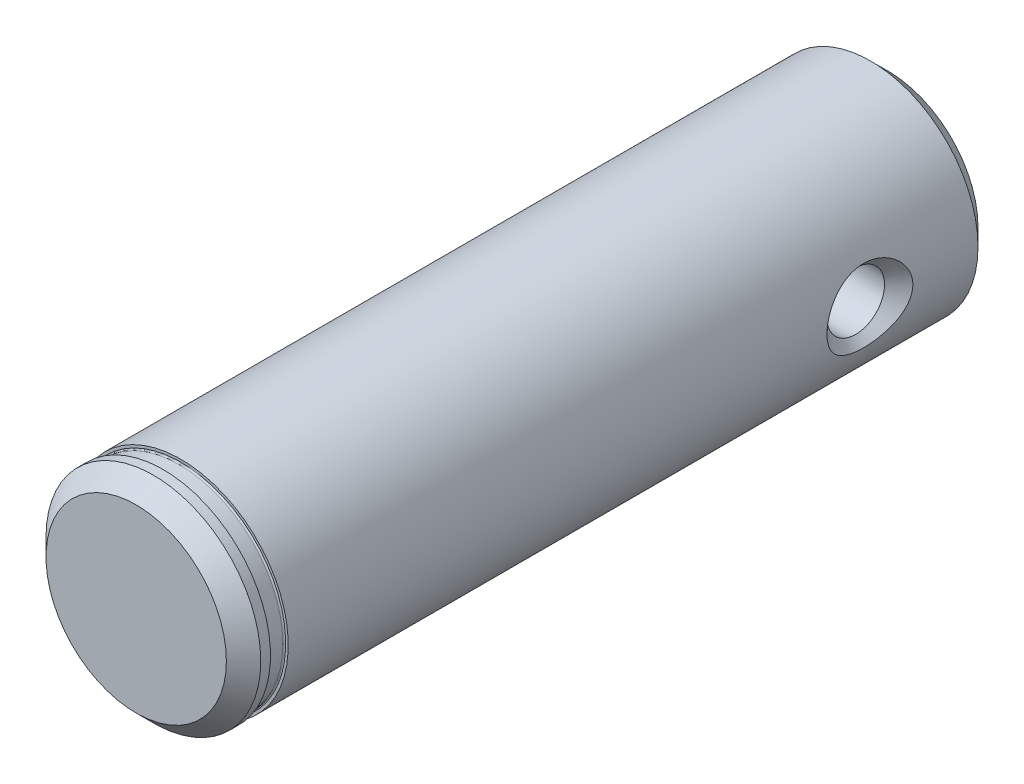
SolidWorks part; units mm, degrees
note: '?' marks a value the reader was unsure of.
ref_plane "Front Plane" through (0, 0, 0) normal (0, 0, 1) x (1, 0, 0)
ref_plane "Top Plane" through (0, 0, 0) normal (0, 1, 0) x (1, 0, 0)
ref_plane "Right Plane" through (0, 0, 0) normal (1, 0, 0) x (0, 0, -1)
sketch "Sketch1" plane through (0, 0, 0) normal (0, 0, 1) x (1, 0, 0)
  circle A0 centre (0, 0) radius 9.525
  dimension "D1" = 19.05
extrude "Boss-Extrude1" add sketch "Sketch1" along normal mid plane 66.675
ref_plane "Plane1" through (-9.525, 0, 0) normal (-1, 0, 0) x (0, 0, 1)
chamfer "Chamfer1" distance 1.524 angle 45 2 edges at (9.525, 0, -33.3375) (9.525, 0, 33.3375)
hole_wizard "1/4-20 Tapped Hole1" positions "Sketch4" profile "Sketch3" tap size "1/4-20" standard "ANSI Inch" end condition through all
sketch "Sketch4" plane through (-9.525, 0, 0) normal (-1, 0, 0) x (0, 0, 1)
  line L0 (-33.3375, 8.001) -> (-33.3375, -8.001) construction
  point P0 (-22.225, 0)
  dimension "D1" = 11.1125
sketch "Sketch3" plane through (-9.525, 0, -22.225) normal (0, 1, 0) x (0, 0, 1)
  line L0 (0, 0) -> (0, 19.05)
  line L1 (0, 19.05) -> (3.81, 19.05)
  line L2 (2.5527, 17.7927) -> (2.5527, 1.2573)
  line L3 (2.5527, 1.2573) -> (3.81, 0)
  line L5 (3.81, 0) -> (0, 0)
  line L6 (-2.5527, 1.2573) -> (-3.81, 0) construction
  line L7 (3.81, 19.05) -> (2.5527, 17.7927)
  line L8 (-3.81, 19.05) -> (-2.5527, 17.7927) construction
  line L11 (0, -6.35) -> (0, 107.95) construction
  dimension "Thru Tap Drill Dia." = 5.1054
  dimension "Thru Tap Drill Depth" = 19.05
  dimension "Near C'Sink Dia." = 7.62
  dimension "Near C'Sink Angle" = 90
  dimension "Far C'Sink Dia." = 7.62
  dimension "Far C'Sink Angle" = 90
cosmetic thread "Hole Thread1" parameters "D2"=6.35
sketch3d "3DSketch1"
  point P0 (9.1844, 2.5242, 28.8695)
ref_axis "Axis1" through (0, 0, 31.8135) along (0, 0, -1)?
ref_plane "Plane5" through (0, 0, 0) normal (0.265, -0.9642, 0) x (-0.9161, -0.2518, -0.3122)
sketch "Groove Sketch" plane through (9.5132, 2.6146, 39.1232) normal (0.265, -0.9642, 0) x (-0.301, -0.0827, 0.95)
  line L0 (-1.7828, 20.7562) -> (-1.7114, 20.9734)
  line L1 (-1.7114, 20.9734) -> (-3.2075, 21.465)
  line L2 (-3.2075, 21.465) -> (-3.2789, 21.2478)
  line L3 (-3.1979, 21.0875) -> (-1.9431, 20.6752)
  line L4 (17.9327, 4.4922) -> (-11.7249, 14.2378) construction
  line L5 (-4.9144, 3.5779) -> (0.0811, 18.7802) construction
  line L6 (-3.8645, 11.6548) -> (-64.3116, 31.5178) construction
  arc A0 (-1.9431, 20.6752) -> (-1.7828, 20.7562) centre (-1.9035, 20.7959) ccw
  arc A1 (-3.1979, 21.0875) -> (-3.2789, 21.2478) centre (-3.1582, 21.2082) cw
  point P10 (-2.5705, 20.8814)
  dimension "Radius" = 0.127
  dimension "ID" = 18.3388
  dimension "OD" = 19.05
  dimension "Width" = 1.5748
  dimension "Location" = 3.175
revolve "Retaining Ring Groove" cut sketch "Groove Sketch" angle 360 about L4 reverse direction yes
other "lt duty ext spiral<1>"
